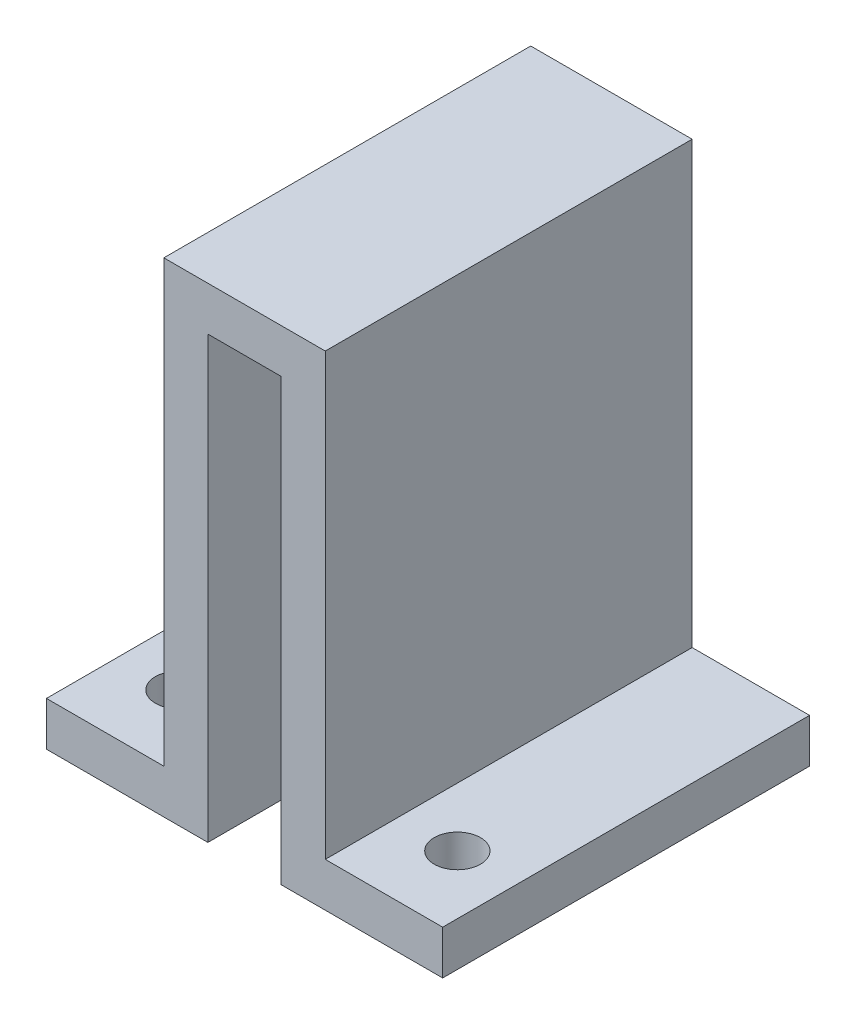
SolidWorks part; units mm, degrees
ref_plane "Front Plane" through (0, 0, 0) normal (0, 0, 1) x (1, 0, 0)
ref_plane "Top Plane" through (0, 0, 0) normal (0, 1, 0) x (1, 0, 0)
ref_plane "Right Plane" through (0, 0, 0) normal (1, 0, 0) x (0, 0, -1)
sketch "Sketch1" plane through (0, 0, 0) normal (0, 0, 1) x (1, 0, 0)
  line L0 (-3.175, 0) -> (3.175, 0)
  line L1 (3.175, 0) -> (3.175, -38.1)
  line L2 (3.175, -38.1) -> (17.145, -38.1)
  line L4 (6.985, 3.81) -> (-6.985, 3.81)
  line L6 (-17.145, -38.1) -> (-3.175, -38.1)
  line L7 (-3.175, -38.1) -> (-3.175, 0)
  line L8 (17.145, -38.1) -> (17.145, -34.29)
  line L9 (17.145, -34.29) -> (6.985, -34.29)
  line L10 (6.985, -34.29) -> (6.985, 3.81)
  line L11 (-6.985, 3.81) -> (-6.985, -34.29)
  line L12 (-6.985, -34.29) -> (-17.145, -34.29)
  line L13 (-17.145, -34.29) -> (-17.145, -38.1)
  line L14 (0, 0) -> (0, 3.81) construction
  dimension "D1" = 6.35
  dimension "D2" = 38.1
  dimension "D3" = 3.81
  dimension "D4" = 3.81
  dimension "D5" = 3.81
  dimension "D6" = 10.16
extrude "Boss-Extrude1" add sketch "Sketch1" along normal blind 31.75
sketch "Sketch2" plane through (0, -38.1, 0) normal (0, -1, 0) x (1, 0, 0)
  line L0 (17.145, 31.75) -> (17.145, 0) construction
  line L1 (3.175, 31.75) -> (17.145, 31.75) construction
  line L2 (0, 31.75) -> (0, 0) construction
  line L3 (-3.175, 31.75) -> (3.175, 31.75) construction
  circle A0 centre (12.065, 25.4) radius 2
  circle A1 centre (-12.065, 25.4) radius 2
  dimension "D1" = 4
  dimension "D2" = 5.08
  dimension "D3" = 6.35
extrude "Cut-Extrude1" cut sketch "Sketch2" against normal through all contours A1 | A0 region at (-12.065, -38.1, 25.4)
